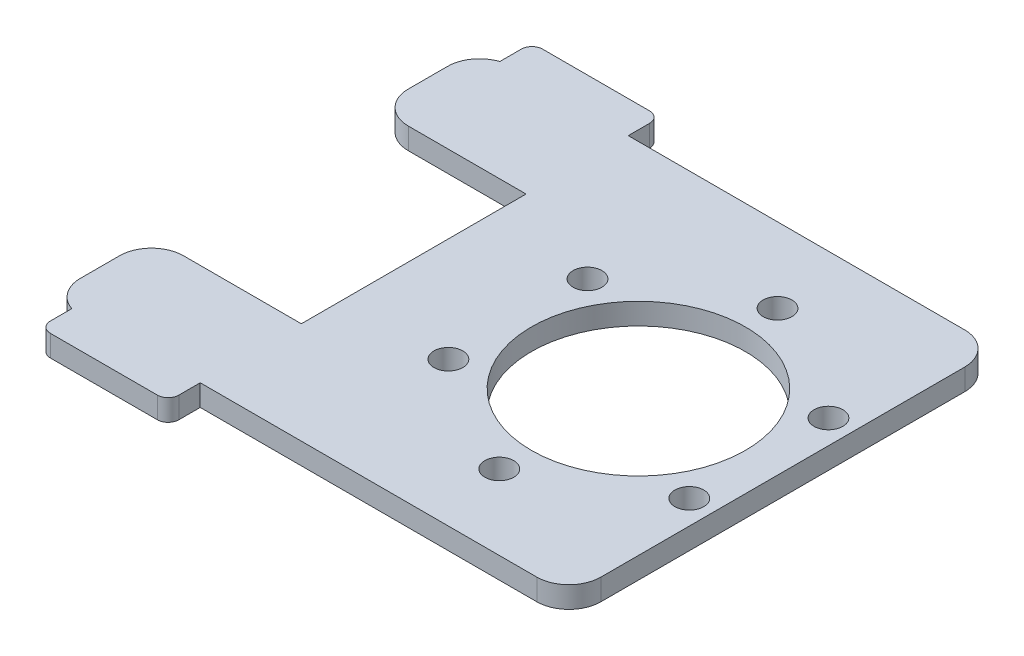
SolidWorks part; units mm, degrees
ref_plane "前视基准面" through (0, 0, 0) normal (0, 0, 1) x (1, 0, 0)
ref_plane "上视基准面" through (0, 0, 0) normal (0, 1, 0) x (1, 0, 0)
ref_plane "右视基准面" through (0, 0, 0) normal (1, 0, 0) x (0, 0, -1)
sketch "草图1" plane through (0, 0, 0) normal (0, 1, 0) x (1, 0, 0)
  line L1 (-24.25, -20) -> (24.25, -20)
  line L2 (-24.25, -20) -> (-24.25, 20)
  line L3 (-24.25, 20) -> (24.25, 20)
  line L4 (24.25, -20) -> (24.25, 20)
  line L5 (-24.25, -20) -> (24.25, 20) construction
  line L6 (-24.25, 20) -> (24.25, -20) construction
  line L7 (-24.25, 10.5) -> (-10.25, 10.5)
  line L8 (-24.25, 10.5) -> (-24.25, -10.5)
  line L9 (-24.25, -10.5) -> (-10.25, -10.5)
  line L10 (-10.25, 10.5) -> (-10.25, -10.5)
  line L11 (-22.2, 20) -> (-10.2, 20)
  line L12 (-22.2, 20) -> (-22.2, 23)
  line L13 (-22.2, 23) -> (-10.2, 23)
  line L14 (-10.2, 20) -> (-10.2, 23)
  line L15 (-22.2, -20) -> (-10.2, -20)
  line L16 (-22.2, -20) -> (-22.2, -23)
  line L17 (-22.2, -23) -> (-10.2, -23)
  line L18 (-10.2, -20) -> (-10.2, -23)
  circle A0 centre (10.75, 0) radius 10
  arc A1 (22.6217, -5.2974) -> (22.6217, 5.2974) centre (10.75, 0) ccw
  arc A2 (9.4018, 12.9299) -> (0.2265, 7.6325) centre (10.75, 0) ccw
  circle A3 centre (10.75, 13) radius 1.35
  circle A4 centre (22.0083, 6.5) radius 1.35
  circle A5 centre (22.0083, -6.5) radius 1.35
  circle A6 centre (10.75, -13) radius 1.35
  circle A7 centre (-0.5083, -6.5) radius 1.35
  circle A8 centre (-0.5083, 6.5) radius 1.35
  arc A9 (21.2735, 7.6325) -> (12.0982, 12.9299) centre (10.75, 0) ccw
  arc A10 (0.2265, -7.6325) -> (9.4018, -12.9299) centre (10.75, 0) ccw
  arc A11 (-1.1217, 5.2974) -> (-1.1217, -5.2974) centre (10.75, 0) ccw
  arc A12 (12.0982, -12.9299) -> (21.2735, -7.6325) centre (10.75, 0) ccw
  point P0 (0, 0)
  dimension "D7" = 2.05
  dimension "D1" = 48.5
  dimension "D2" = 40
  dimension "D3" = 9.5
  dimension "D4" = 9.5
  dimension "D5" = 14
  dimension "D6" = 13.5
  dimension "D8" = 2.05
  dimension "D9" = 12
  dimension "D10" = 12
  dimension "D11" = 3
  dimension "D12" = 3
extrude "凸台-拉伸1" add sketch "草图1" along normal blind 2 contours L7 L10 L9 L2 L1 L4 L3 A12 A6 A10 A7 A11 A8 A2 A3 A9 A4 A1 A5 | L3 L14 L13 L12 | L18 L1 L16 L17 | A6 A12 A5 A1 A4 A9 A3 A2 A8 A11 A7 A10 A0 region at (-23.6213, 0, 15.25) region at (-16.2, 0, 21.5) region at (-16.2, 0, -21.5) region at (20.5216, 0, 5.6416)
fillet "圆角1" radius 3 6 edges at (-24.25, 1, -20) (-24.25, 1, -10.5) (-24.25, 1, 20) (-24.25, 1, 10.5) (24.25, 1, 20) (24.25, 1, -20)
fillet "圆角2" radius 1 4 edges at (-22.2, 1, -23) (-10.2, 1, -23) (-22.2, 1, 23) (-10.2, 1, 23)
